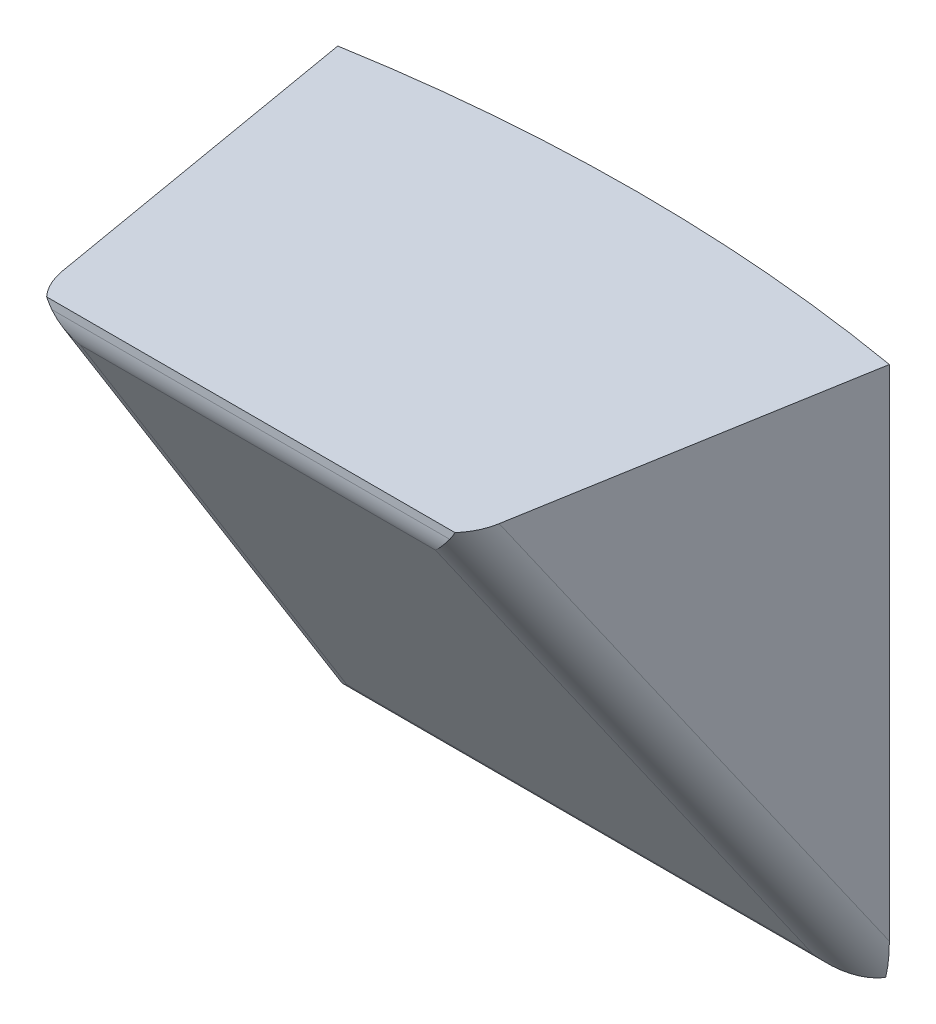
SolidWorks part; units mm, degrees
ref_plane "Front Plane" through (0, 0, 0) normal (0, 0, 1) x (1, 0, 0)
ref_plane "Top Plane" through (0, 0, 0) normal (0, 1, 0) x (1, 0, 0)
ref_plane "Right Plane" through (0, 0, 0) normal (1, 0, 0) x (0, 0, -1)
sketch "Sketch1" plane through (0, 0, 0) normal (0, 1, 0) x (1, 0, 0)
  line L0 (0, 96.8375) -> (0, 0) construction
  line L1 (-12.7, 73.8463) -> (12.7, 73.8463)
  line L2 (-12.7, 73.8463) -> (-16.4137, 95.4363)
  line L3 (12.7, 73.8463) -> (16.4137, 95.4363)
  arc A0 (16.4137, 95.4363) -> (-16.4137, 95.4363) centre (0, 0) ccw
  point P6 (0, 73.8463)
  dimension "D1" = 193.675
  dimension "D2" = 25.4
  dimension "D3" = 21.59
  dimension "D4" = 99.76
extrude "Boss-Extrude1" add sketch "Sketch1" along normal blind 31.75
sketch "Sketch2" plane through (0, 0, 0) normal (1, 0, 0) x (0, 0, -1)
  line L0 (73.8463, 30.48) -> (94.1663, 0)
  line L1 (73.8463, 31.75) -> (73.8463, 0) construction
  line L2 (73.8463, 0) -> (95.4363, 0) construction
  line L3 (94.1663, 0) -> (73.8463, 0)
  line L4 (73.8463, 0) -> (73.8463, 30.48)
  dimension "D1" = 1.27
  dimension "D2" = 1.27
extrude "Cut-Extrude1" cut sketch "Sketch2" against normal through all both and the other way through all
fillet "Fillet1" radius 2.54 4 edges at (14.4476, 15.24, -84.0063) (-14.4476, 15.24, -84.0063) (0, 0, -94.1663) (0, 30.48, -73.8463)
